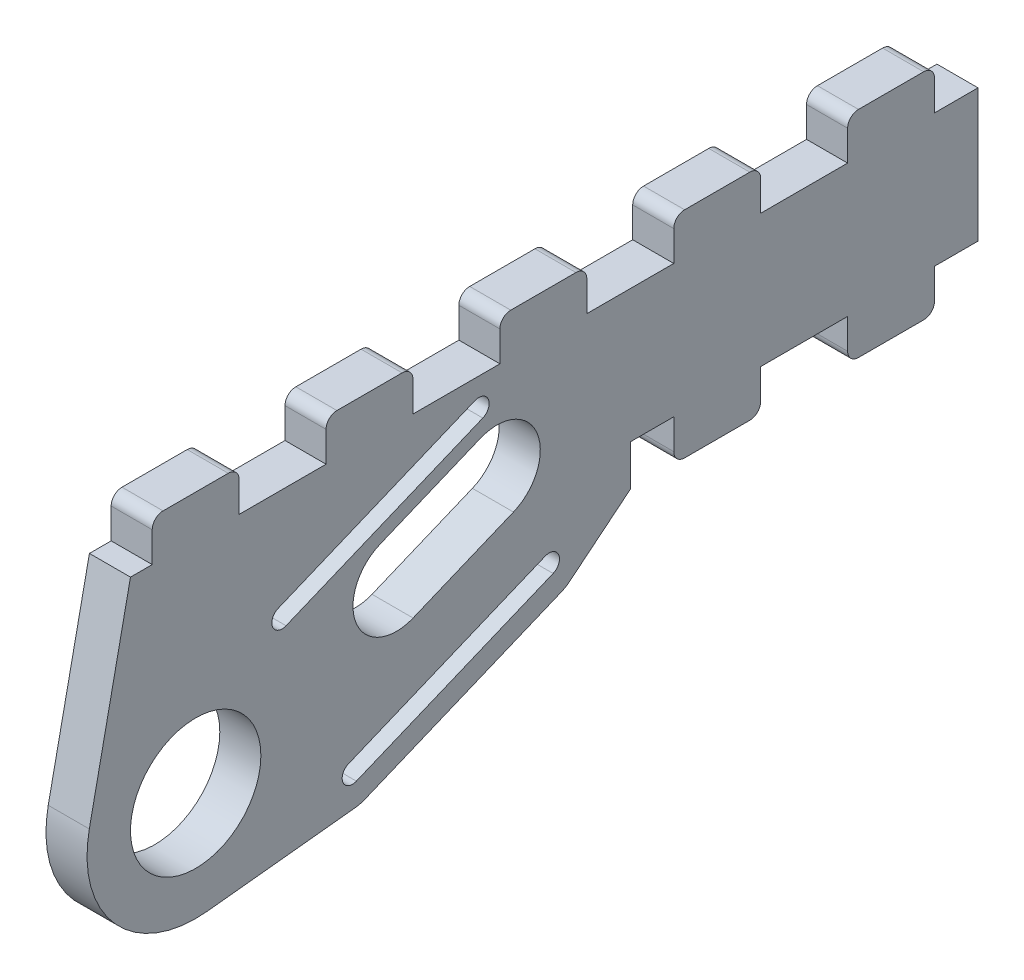
SolidWorks part; units mm, degrees
ref_plane "Front Plane" through (0, 0, 0) normal (0, 0, 1) x (1, 0, 0)
ref_plane "Top Plane" through (0, 0, 0) normal (0, 1, 0) x (1, 0, 0)
ref_plane "Right Plane" through (0, 0, 0) normal (1, 0, 0) x (0, 0, -1)
sketch "Sketch1" plane through (0, 0, 0) normal (1, 0, 0) x (0, 0, -1)
  line L0 (-41.4563, 38.1) -> (38.3452, 38.1) construction
  line L1 (-15.541, 3.2395) -> (-9.525, 32.1)
  line L2 (38.9021, 32.1) -> (-38.9021, 32.1) construction
  line L3 (38.9021, 32.1) -> (38.9021, 38.1) construction
  line L4 (38.9021, 38.1) -> (-38.9021, 38.1) construction
  line L5 (-38.9021, 32.1) -> (-38.9021, 38.1) construction
  line L6 (38.9021, 32.1) -> (-38.9021, 38.1) construction
  line L7 (38.9021, 38.1) -> (-38.9021, 32.1) construction
  line L8 (0, 7.3323) -> (-6.35, 3.6662) construction
  line L9 (-6.35, 3.6662) -> (-6.35, -3.6662) construction
  line L10 (-6.35, -3.6662) -> (0, -7.3323) construction
  line L11 (0, -7.3323) -> (6.35, -3.6662) construction
  line L12 (6.35, -3.6662) -> (6.35, 3.6662) construction
  line L13 (6.35, 3.6662) -> (0, 7.3323) construction
  line L14 (-9.525, 32.1) -> (63.5, 32.1)
  line L15 (0, -15.875) -> (63.5, -15.875)
  line L16 (63.5, -15.875) -> (63.5, 32.1)
  line L18 (157.9971, 6.7) -> (88.9, 6.7) construction
  line L19 (157.9971, 6.7) -> (157.9971, 12.7) construction
  line L20 (157.9971, 12.7) -> (88.9, 12.7) construction
  line L21 (88.9, 6.7) -> (88.9, 12.7) construction
  line L22 (157.9971, 6.7) -> (88.9, 12.7) construction
  line L23 (157.9971, 12.7) -> (88.9, 6.7) construction
  circle A0 centre (0, 0) radius 9.525
  arc A1 (-15.541, 3.2395) -> (0, -15.875) centre (0, 0) ccw
  circle A2 centre (0, 0) radius 25.4 construction
  circle A3 centre (0, 0) radius 6.35 construction
  arc A4 (0, -15.875) -> (-15.541, 3.2395) centre (0, 0) ccw construction
  point P3 (123.4486, 9.7)
  point P7 (0, 35.1)
  point P28 (88.9, 9.7)
  dimension "D1" = 19.05
  dimension "D2" = 6.35
  dimension "D4" = 50.8
  dimension "D3" = 38.1
  dimension "D5" = 6
  dimension "D6" = 12.7
  dimension "D7" = 9.525
  dimension "D8" = 63.5
  dimension "D9" = 25.4
  dimension "D10" = 88.9
extrude "Boss-Extrude1" add sketch "Sketch1" along normal mid plane 6
sketch "Sketch2" plane through (3, 0, 0) normal (1, 0, 0) x (0, 0, -1)
  line L0 (0, 0) -> (35.1998, 14.5802) construction
  line L1 (1.6762, -15.7863) -> (23.3965, -13.4799)
  line L2 (29.3332, 12.1502) -> (43.9998, 18.2253) construction
  line L3 (26.9031, 18.0168) -> (41.5697, 24.0919)
  line L4 (31.7632, 6.2836) -> (46.4298, 12.3587)
  line L5 (22.9029, -8.8311) -> (51.6494, 3.0761) construction
  line L6 (22.3289, -7.4452) -> (51.0754, 4.4619)
  line L7 (23.4769, -10.2169) -> (52.2234, 1.6903)
  line L8 (12.6291, 15.9721) -> (41.3756, 27.8793) construction
  line L9 (12.055, 17.358) -> (40.8015, 29.2651)
  line L10 (13.2031, 14.5863) -> (41.9496, 26.4935)
  line L11 (12.6291, 15.9721) -> (22.9029, -8.8311) construction
  line L12 (41.3756, 27.8793) -> (51.6494, 3.0761) construction
  line L13 (28.6437, 8.0763) -> (36.8154, 18.7257) construction
  line L14 (42.9639, 14.0078) -> (30.6669, 23.4436) construction
  line L15 (30.6669, 23.4436) -> (16.3468, 17.5121) construction
  line L16 (16.3468, 17.5121) -> (14.3236, 2.1447) construction
  line L17 (14.3236, 2.1447) -> (26.6206, -7.2911) construction
  line L18 (26.6206, -7.2911) -> (40.9407, -1.3595) construction
  line L19 (40.9407, -1.3595) -> (42.9639, 14.0078) construction
  line L20 (21.1138, -4.5119) -> (49.8603, 7.3953) construction
  line L21 (24.6919, -13.1502) -> (53.4384, -1.243) construction
  line L22 (0, 0) -> (15.49, 0) construction
  line L23 (0, -15.875) -> (63.5, -15.875)
  line L24 (63.5, -15.875) -> (63.5, 6.7)
  line L25 (63.5, -15.875) -> (63.5, 32.1) construction
  line L26 (63.5, 6.7) -> (54.602, -0.5484)
  line L27 (53.4384, -1.243) -> (24.6919, -13.1502)
  arc A0 (26.9031, 18.0168) -> (31.7632, 6.2836) centre (29.3332, 12.1502) ccw
  arc A1 (46.4298, 12.3587) -> (41.5697, 24.0919) centre (43.9998, 18.2253) ccw
  arc A2 (22.3289, -7.4452) -> (23.4769, -10.2169) centre (22.9029, -8.8311) ccw
  arc A3 (52.2234, 1.6903) -> (51.0754, 4.4619) centre (51.6494, 3.0761) ccw
  arc A4 (12.055, 17.358) -> (13.2031, 14.5863) centre (12.6291, 15.9721) ccw
  arc A5 (41.9496, 26.4935) -> (40.8015, 29.2651) centre (41.3756, 27.8793) ccw
  circle A6 centre (32.9051, 13.6297) radius 6.477 construction
  circle A7 centre (28.6437, 8.0763) radius 13.4234 construction
  arc A8 (53.4384, -1.243) -> (49.8603, 7.3953) centre (51.6494, 3.0761) ccw construction
  arc A9 (21.1138, -4.5119) -> (24.6919, -13.1502) centre (22.9029, -8.8311) ccw construction
  circle A10 centre (0, 0) radius 15.875 construction
  arc A13 (-15.541, 3.2395) -> (0, -15.875) centre (0, 0) ccw construction
  arc A14 (1.6762, -15.7863) -> (0, -15.875) centre (0, 0) cw
  arc A15 (54.602, -0.5484) -> (53.4384, -1.243) centre (51.6494, 3.0761) cw
  arc A16 (24.6919, -13.1502) -> (23.3965, -13.4799) centre (22.9029, -8.8311) cw
  point P7 (36.6665, 15.1877)
  point P14 (37.2761, -2.8775)
  point P19 (27.0023, 21.9257)
  dimension "D2" = 12.7
  dimension "D5" = 1.5
  dimension "D8" = 12.954
  dimension "D1" = 38.1
  dimension "D3" = 15.875
  dimension "D4" = 31.75
  dimension "D6" = 31
  dimension "D7" = 7
  dimension "D9" = 13.97
  dimension "D10" = 1.27
  dimension "D12" = 22.5
  dimension "D13" = 25.4
  dimension "D11" = 3.175
extrude "Cut-Extrude1" cut sketch "Sketch2" against normal through all
sketch "Sketch4" plane through (3, 0, 0) normal (1, 0, 0) x (0, 0, -1)
  line L0 (157.9971, 12.7) -> (88.9, 12.7) construction
  line L1 (63.5, 32.1) -> (114.3, 32.1)
  line L2 (63.5, 32.1) -> (63.5, 12.7)
  line L3 (63.5, 12.7) -> (114.3, 12.7)
  line L4 (114.3, 32.1) -> (114.3, 12.7)
  line L5 (88.9, 6.7) -> (88.9, 12.7) construction
  dimension "D1" = 25.4
extrude "Boss-Extrude3" add sketch "Sketch4" against normal up to surface (6 mm away) up to face at (-3, -2.8775, -37.2761)
sketch "Sketch3" plane through (0, 32.1, 0) normal (0, 1, 0) x (1, 0, 0)
  line L0 (3, 114.3) -> (3, -9.525) construction
  line L1 (-3, -6.35) -> (3, -6.35)
  line L2 (-3, -6.35) -> (-3, 6.35)
  line L3 (-3, 6.35) -> (3, 6.35)
  line L4 (3, -6.35) -> (3, 6.35)
  line L5 (-3, -6.35) -> (3, 6.35) construction
  line L6 (-3, 6.35) -> (3, -6.35) construction
  point P0 (0, 0)
  dimension "D1" = 12.7
extrude "Boss-Extrude2" add sketch "Sketch3" along normal blind 6
fillet "Fillet1" radius 1.5875 2 edges at (0, 38.1, -6.35) (0, 38.1, 6.35)
pattern_linear "LPattern1" count 5 spacing 25.4 along (0, 0, -1) of "Boss-Extrude2", "Fillet1"
sketch "Sketch5" plane through (-3, 0, 0) normal (-1, 0, 0) x (0, 0, 1)
  line L0 (-114.3, 12.7) -> (-63.5, 12.7) construction
  line L1 (-69.85, 12.7) -> (-82.55, 12.7)
  line L2 (-69.85, 12.7) -> (-69.85, 6.7)
  line L3 (-69.85, 6.7) -> (-82.55, 6.7)
  line L4 (-82.55, 12.7) -> (-82.55, 6.7)
  line L5 (-69.85, 36.5125) -> (-69.85, 32.1) construction
  line L6 (-82.55, 36.5125) -> (-82.55, 32.1) construction
  dimension "D1" = 6
extrude "Boss-Extrude4" add sketch "Sketch5" against normal up to surface (6 mm away) up to face at (3, -2.8775, -37.2761)
fillet "Fillet2" radius 1.5875 2 edges at (0, 6.7, -69.85) (0, 6.7, -82.55)
pattern_linear "LPattern2" count 2 spacing 25.4 along (0, 0, -1) of "Boss-Extrude4", "Fillet2"
equation "\"D6@Sketch2\"=31mm"
equation "\"D7@Sketch2\"=7mm"
